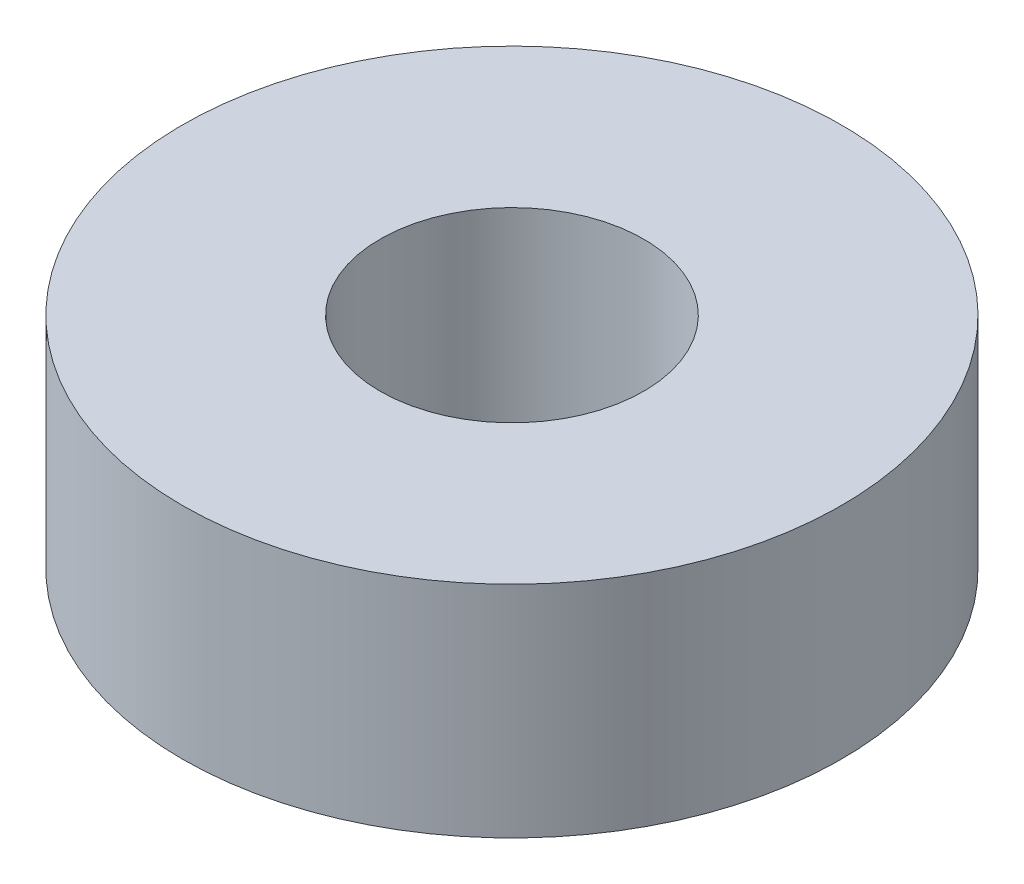
SolidWorks part; units mm, degrees
ref_plane "Front Plane" through (0, 0, 0) normal (0, 0, 1) x (1, 0, 0)
ref_plane "Top Plane" through (0, 0, 0) normal (0, 1, 0) x (1, 0, 0)
ref_plane "Right Plane" through (0, 0, 0) normal (1, 0, 0) x (0, 0, -1)
sketch "Sketch1" plane through (0, 0, 0) normal (0, 1, 0) x (1, 0, 0)
  circle A0 centre (0, 0) radius 3
  circle A1 centre (0, 0) radius 7.5
  dimension "D1" = 6
  dimension "D2" = 15
extrude "Boss-Extrude1" add sketch "Sketch1" along normal blind 5 contours A1
extrude "Cut-Extrude1" cut sketch "Sketch1<3>" along normal up to surface (5 mm away) contours A0 up to face at (0, 5, 7.5)
sketch "Sketch1<3>" plane through (0, 0, 0) normal (0, 1, 0) x (1, 0, 0) same geometry as "Sketch1"
